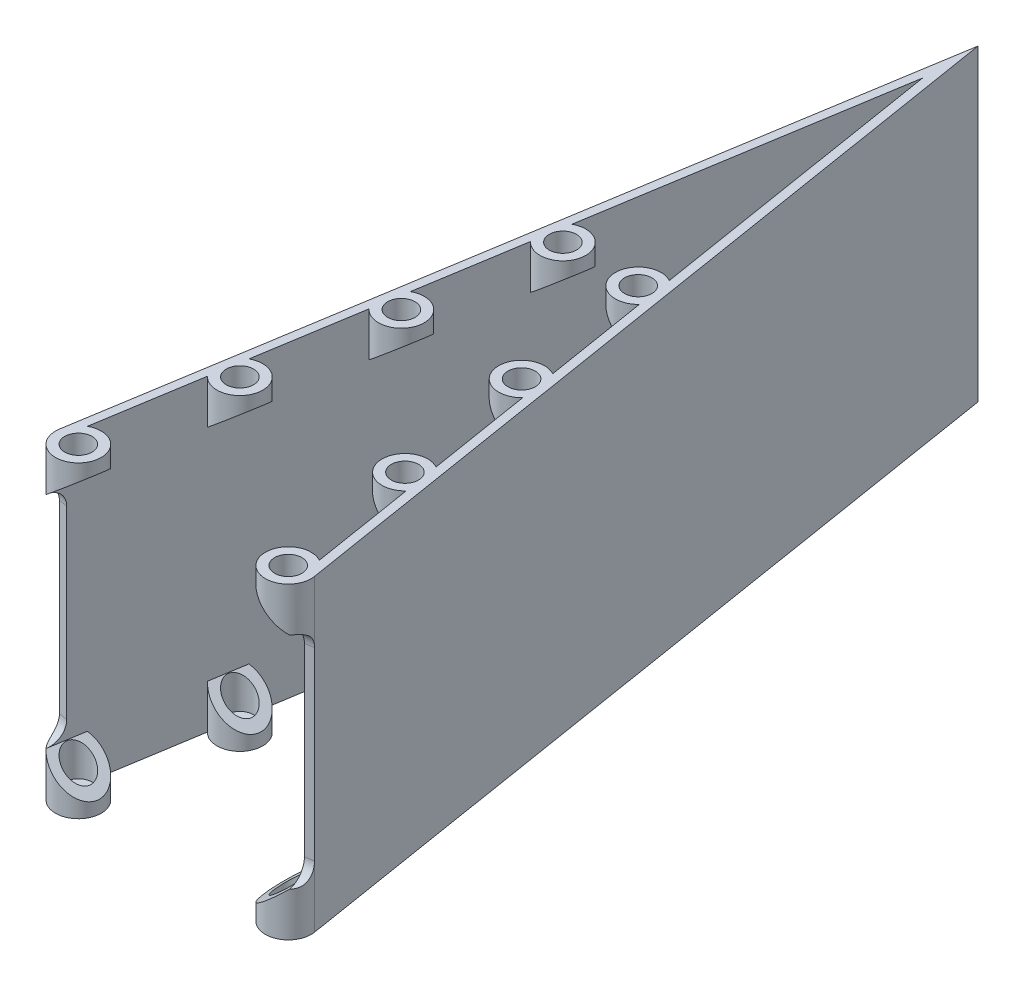
SolidWorks part; units mm, degrees
ref_plane "Front Plane" through (0, 0, 0) normal (0, 0, 1) x (1, 0, 0)
ref_plane "Top Plane" through (0, 0, 0) normal (0, 1, 0) x (1, 0, 0)
ref_plane "Right Plane" through (0, 0, 0) normal (1, 0, 0) x (0, 0, -1)
sketch "Sketch1" plane through (0, 0, 0) normal (0, 1, 0) x (1, 0, 0)
  line L0 (-13.5, 0) -> (13.5, 0) construction
  line L1 (-13.5, 0) -> (0, 83.7185)
  line L2 (0, 83.7185) -> (13.5, 0)
  line L3 (13.5, 0) -> (14.4872, 0.1592)
  line L4 (14.4872, 0.1592) -> (0, 90)
  line L5 (0, 90) -> (-14.4872, 0.1592)
  line L6 (-14.4872, 0.1592) -> (-13.5, 0)
  point P2 (0, 0)
  dimension "D1" = 90
  dimension "D2" = 90
  dimension "D4" = 1
  dimension "D5" = 27
  dimension "D3" = 90
extrude "Boss-Extrude1" add sketch "Sketch1" along normal blind 35
sketch "Sketch2" plane through (0, 0, 0) normal (0, 1, 0) x (1, 0, 0)
  line L0 (0, -1000) -> (0, 49000) construction
  line L1 (0, 83.7185) -> (13.5, 0) construction
  line L2 (0, 83.7185) -> (13.5, 0) construction
  line L3 (11.9204, -0.2547) -> (13.5, 0) construction
  line L4 (13.5, 0) -> (14.4872, 0.1592) construction
  line L5 (14.4872, 0.1592) -> (0, 90) construction
  line L6 (14.4872, 0.1592) -> (0, 90) construction
  circle A0 centre (11.9204, -0.2547) radius 2.6
  circle A1 centre (11.9204, -0.2547) radius 1.55
  circle A22 centre (9.3732, 15.5412) radius 1.55
  circle A23 centre (9.3732, 15.5412) radius 2.6
  circle A24 centre (6.8261, 31.3372) radius 1.55
  circle A25 centre (6.8261, 31.3372) radius 2.6
  circle A26 centre (4.2789, 47.1331) radius 1.55
  circle A27 centre (4.2789, 47.1331) radius 2.6
  circle A28 centre (-4.2789, 47.1331) radius 2.6
  circle A29 centre (-4.2789, 47.1331) radius 1.55
  circle A30 centre (-6.8261, 31.3372) radius 2.6
  circle A31 centre (-6.8261, 31.3372) radius 1.55
  circle A32 centre (-9.3732, 15.5412) radius 2.6
  circle A33 centre (-9.3732, 15.5412) radius 1.55
  circle A34 centre (-11.9204, -0.2547) radius 2.6
  circle A35 centre (-11.9204, -0.2547) radius 1.55
  dimension "D1" = 5.2
  dimension "D2" = 3.1
  dimension "D4" = 16
  dimension "D3" = 4
extrude "Boss-Extrude3" add sketch "Sketch2" along normal blind 5
sketch "Sketch4" plane through (0.3421, 0, 2.1218) normal (0.1592, 0, 0.9872) x (0.9872, 0, -0.1592)
  line L0 (9.1278, 5) -> (9.1278, 0) construction
  line L1 (14.3278, 5) -> (9.1278, 5) construction
  line L2 (13.3278, 35) -> (13.3278, 0) construction
  line L3 (9.1278, 5) -> (9.1278, 0) construction
  line L4 (14.3278, 5) -> (9.1278, 5) construction
  line L5 (13.3278, 35) -> (13.3278, 0) construction
  line L6 (13.3278, 5) -> (9.1278, 1.4758)
  line L7 (13.3278, 5) -> (9.1278, 5)
  line L8 (9.1278, 5) -> (9.1278, 1.4758)
  dimension "D1" = 40
extrude "Cut-Extrude1" cut sketch "Sketch4" against normal up to surface and the other way through all contours L7 L8 L6 up to face at (-8.5675, 6.1111, -30.5881)
sketch "Sketch5" plane through (-0.3421, 0, 2.1218) normal (-0.1592, 0, 0.9872) x (0.9872, 0, 0.1592)
  line L0 (-9.1278, 0) -> (-9.1278, 5) construction
  line L1 (-9.1278, 5) -> (-14.3278, 5) construction
  line L2 (-13.3278, 35) -> (-13.3278, 0) construction
  line L3 (-9.1278, 0) -> (-9.1278, 5) construction
  line L4 (-9.1278, 5) -> (-14.3278, 5) construction
  line L5 (-13.3278, 35) -> (-13.3278, 0) construction
  line L6 (-13.3278, 5) -> (-9.1278, 1.4758)
  line L7 (-13.3278, 5) -> (-9.1278, 5)
  line L8 (-9.1278, 5) -> (-9.1278, 1.4758)
  dimension "D1" = 40
extrude "Cut-Extrude2" cut sketch "Sketch5" against normal up to surface and the other way through all contours L8 L7 L6 up to face at (8.5675, 6.1111, -30.5881)
ref_plane "Plane1" through (0, 17.5, 0) normal (0, 1, 0) x (1, 0, 0)
mirror "Mirror2" about plane through (0, 17.5, 0) normal (0, 1, 0) of "Cut-Extrude2", "Cut-Extrude1", "Boss-Extrude3"
fillet "Fillet1" radius 2 4 edges at (13.9936, 5, -0.0796) (13.9936, 30, -0.0796) (-13.9936, 5, -0.0796) (-13.9936, 30, -0.0796)
sketch "Sketch6" plane through (0, 0, 0) normal (0, -1, 0) x (1, 0, 0)
  arc A1 (14.4872, -0.1592) -> (13.1737, -2.0233) centre (11.9204, 0.2547) ccw construction
  arc A2 (11.2791, -13.7727) -> (10.6266, -17.8192) centre (9.3732, -15.5412) ccw construction
  arc A5 (8.7319, -29.5686) -> (8.0794, -33.6151) centre (6.8261, -31.3372) ccw construction
  arc A6 (6.1847, -45.3646) -> (5.5322, -49.4111) centre (4.2789, -47.1331) ccw construction
  arc A10 (-5.5322, -49.4111) -> (-6.1847, -45.3646) centre (-4.2789, -47.1331) ccw construction
  arc A11 (14.4872, -0.1592) -> (13.1737, -2.0233) centre (11.9204, 0.2547) ccw
  arc A12 (11.2791, -13.7727) -> (10.6266, -17.8192) centre (9.3732, -15.5412) ccw
  arc A13 (-8.0794, -33.6151) -> (-8.7319, -29.5686) centre (-6.8261, -31.3372) ccw construction
  arc A14 (-10.6266, -17.8192) -> (-11.2791, -13.7727) centre (-9.3732, -15.5412) ccw construction
  arc A15 (8.7319, -29.5686) -> (8.0794, -33.6151) centre (6.8261, -31.3372) ccw
  arc A16 (6.1847, -45.3646) -> (5.5322, -49.4111) centre (4.2789, -47.1331) ccw
  arc A17 (-13.1737, -2.0233) -> (-14.4872, -0.1592) centre (-11.9204, 0.2547) ccw construction
  arc A18 (-5.5322, -49.4111) -> (-6.1847, -45.3646) centre (-4.2789, -47.1331) ccw
  arc A19 (-8.0794, -33.6151) -> (-8.7319, -29.5686) centre (-6.8261, -31.3372) ccw
  circle A22 centre (4.2789, -47.1331) radius 2.6
  circle A24 centre (6.8261, -31.3372) radius 2.6
  circle A27 centre (9.3732, -15.5412) radius 2.6
  circle A28 centre (11.9204, 0.2547) radius 2.6
  arc A30 (-10.6266, -17.8192) -> (-11.2791, -13.7727) centre (-9.3732, -15.5412) ccw
  arc A31 (-13.1737, -2.0233) -> (-14.4872, -0.1592) centre (-11.9204, 0.2547) ccw
  circle A32 centre (-11.9204, 0.2547) radius 2.6
  circle A33 centre (-9.3732, -15.5412) radius 2.6
  circle A34 centre (-6.8261, -31.3372) radius 2.6
  circle A35 centre (-4.2789, -47.1331) radius 2.6
extrude "Boss-Extrude4" add sketch "Sketch6" against normal blind 1
equation "\"D2@Sketch1\"=\"D1@Sketch1\""
